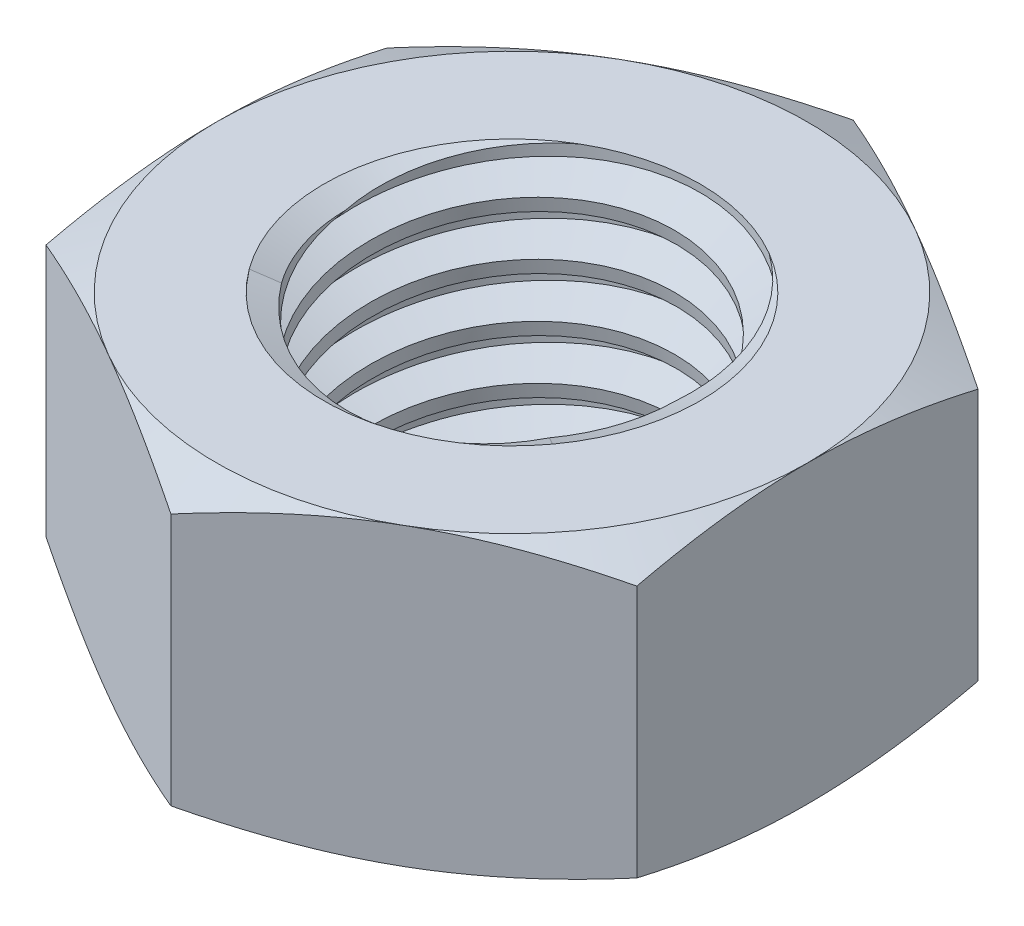
SolidWorks part; units mm, degrees
ref_plane "Front" through (0, 0, 0) normal (0, 0, 1) x (1, 0, 0)
ref_plane "Top" through (0, 0, 0) normal (0, 1, 0) x (1, 0, 0)
ref_plane "Right" through (0, 0, 0) normal (1, 0, 0) x (0, 0, -1)
sketch "Sketch1" plane through (0, 0, 0) normal (0, 1, 0) x (1, 0, 0)
  line L1 (0, 12.7017) -> (-11, 6.3509)
  line L2 (-11, 6.3509) -> (-11, -6.3509)
  line L3 (-11, -6.3509) -> (0, -12.7017)
  line L4 (0, -12.7017) -> (11, -6.3509)
  line L5 (11, -6.3509) -> (11, 6.3509)
  line L6 (11, 6.3509) -> (0, 12.7017)
  circle A0 centre (0, 0) radius 11 construction
  dimension "Hex Flats" = 22
extrude "Extrude1" add sketch "Sketch1" along normal mid plane 11
sketch "Sketch2" plane through (0, 0, 0) normal (1, 0, 0) x (0, 0, -1)
  line L0 (-7, -5.5) -> (-7, 5.5) construction
  line L1 (0, -5.5) -> (7, -5.5)
  line L2 (0, -5.5) -> (0, 5.5)
  line L3 (0, 5.5) -> (7, 5.5)
  line L4 (7, -5.5) -> (7, 5.5)
  line L5 (-6.3509, 5.5) -> (6.3509, 5.5) construction
  line L6 (-6.3509, -5.5) -> (6.3509, -5.5) construction
  line L7 (0, -12.5) -> (0, -5.5) construction
  dimension "Thread Dia" = 14
revolve "Revolve1" add sketch "Sketch2" angle 360 about L7
sketch "Sketch3" plane through (0, 0, 0) normal (1, 0, 0) x (0, 0, -1)
  line L0 (7, 5.5) -> (-7, 5.5) construction
  line L1 (-7, 5.5) -> (-7, 3.5) construction
  line L2 (-7, 3.5) -> (7, 5.5) construction
  line L3 (7, 5.5) -> (7.0354, 5.2525) construction
  line L4 (7.0354, 5.2525) -> (7.2828, 3.5201)
  line L5 (7.2828, 3.5201) -> (6.1228, 3.9857)
  line L6 (6.1228, 3.9857) -> (6.0521, 4.4807)
  line L7 (6.0521, 4.4807) -> (7.0354, 5.2525)
  line L8 (6.0874, 4.2332) -> (7.1591, 4.3863) construction
  line L9 (7, 5.5) -> (7, 4.3636) construction
  line L10 (7, 4.3636) -> (-7, 2.3636) construction
  line L11 (-7, 2.3636) -> (-7, 3.5) construction
  line L12 (-0.3052, 5.5) -> (0.3052, 1.2272) construction
  line L13 (-7, -5.5) -> (-7, 5.5) construction
  line L14 (0, 5.5) -> (7, 5.5) construction
  line L15 (7, -5.5) -> (7, 5.5) construction
  line L16 (0, 0) -> (0, 5.5) construction
  line L17 (-7.0354, 5.2525) -> (-7.2828, 3.5201) construction
  line L18 (-6.0521, 4.4807) -> (-7.0354, 5.2525) construction
  line L19 (-6.1228, 3.9857) -> (-6.0521, 4.4807) construction
  line L20 (-7.2828, 3.5201) -> (-6.1228, 3.9857) construction
  line L21 (0.3052, 5.5) -> (-0.3052, 1.2272) construction
  point P13 (0, 3.3636)
  dimension "D1" = 0.25
  dimension "D2" = 0.5
  dimension "Thread Pitch" = 2
  dimension "D4" = 60
  dimension "D5" = 2
revolve "Cut-Revolve1" cut sketch "Sketch3" angle 360 about L12
pattern_linear "LPattern1" count 6 spacing 2 along (0, -1, 0) count 2 spacing 2 along (0, 1, 0) of "Cut-Revolve1"
sketch "Sketch4" plane through (0, 0, 0) normal (1, 0, 0) x (0, 0, -1)
  line L0 (0, 5.5) -> (7, 5.5)
  line L1 (7, 5.5) -> (6.0521, 5.058)
  line L2 (6.0521, 5.058) -> (6.0521, -5.058)
  line L3 (6.0521, -5.058) -> (7, -5.5)
  line L4 (7, -5.5) -> (0, -5.5)
  line L5 (0, -5.5) -> (0, 5.5)
  line L6 (7, -5.5) -> (7, 5.5) construction
  line L7 (0, 5.5) -> (7, 5.5) construction
  line L8 (0, -5.5) -> (7, -5.5) construction
  line L9 (0, -5.5) -> (0, 5.5) construction
  line L10 (0, 5.5) -> (0, 6.5459) construction
  dimension "D1" = 25
revolve "Cut-Revolve2" cut sketch "Sketch4" angle 360 about L10
combine bodies "Combine1" operation type subtract main body 112 bodies to subtract 111
sketch "Sketch5" plane through (0, 0, 0) normal (1, 0, 0) x (0, 0, -1)
  line L0 (0, -5.5) -> (11, -5.5)
  line L1 (11, -5.5) -> (12.7017, -4.7065)
  line L2 (12.7017, -4.7065) -> (12.7017, 4.7065)
  line L3 (12.7017, 4.7065) -> (11, 5.5)
  line L4 (0, 5.5) -> (0, 6.77)
  line L5 (0, 6.77) -> (13.9717, 6.77)
  line L6 (13.9717, 6.77) -> (13.9717, -6.77)
  line L7 (13.9717, -6.77) -> (0, -6.77)
  line L8 (0, -6.77) -> (0, -5.5)
  line L9 (11, 5.5) -> (11, -5.5) construction
  line L11 (0, -5.5) -> (7, -5.5) construction
  line L12 (11, 5.5) -> (0, 5.5)
  line L13 (12.7017, 0) -> (13.9717, 0) construction
  line L14 (12.7017, 5.5) -> (12.7017, -5.5) construction
  line L15 (0, -5.5) -> (0, 5.5) construction
  line L17 (0, 0) -> (11, 0) construction
  line L22 (0, 5.5) -> (7, 5.5) construction
  dimension "D1" = 25
  dimension "D2" = 1.27
  dimension "D3" = 11
revolve "Cut-Revolve3" cut sketch "Sketch5" angle 360 about L15
equation "\"D1@Sketch3\"=\"Thread Pitch@Sketch3\"/8"
equation "\"D2@Sketch3\"=\"Thread Pitch@Sketch3\"/4"
equation "\"D5@Sketch3\"=\"Thread Pitch@Sketch3\""
equation "\"D4@LPattern1\"=\"Thread Pitch@Sketch3\""
equation "\"D3@LPattern1\"=\"Thread Pitch@Sketch3\""
equation "\"D1@LPattern1\"=\"Height@Extrude1\"/\"Thread Pitch@Sketch3\""
